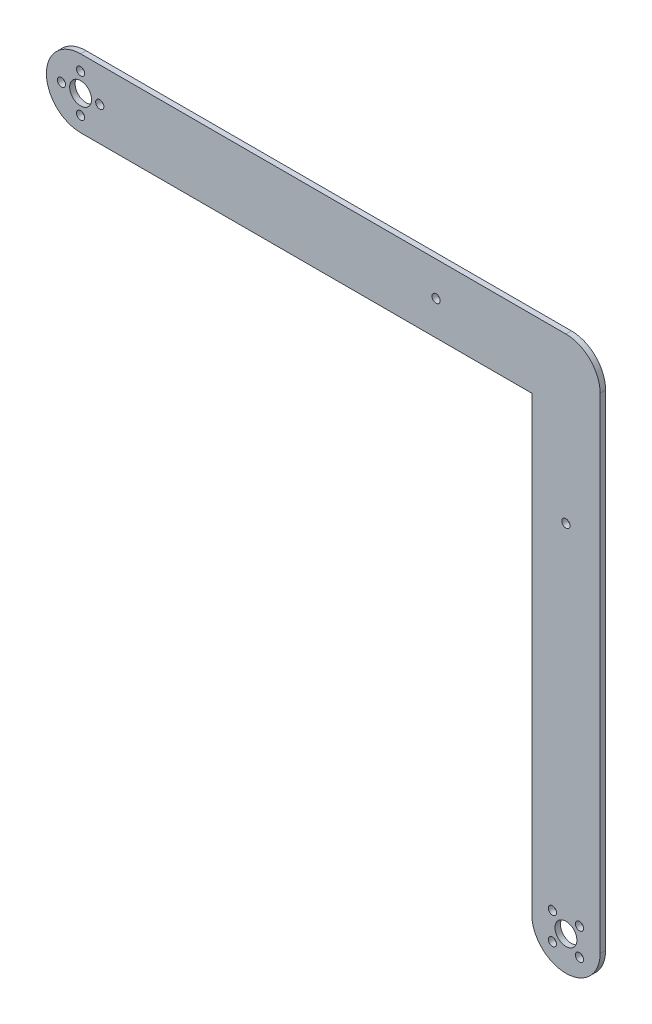
SolidWorks part; units mm, degrees
ref_plane "Front" through (0, 0, 0) normal (0, 0, 1) x (1, 0, 0)
ref_plane "Top" through (0, 0, 0) normal (0, 1, 0) x (1, 0, 0)
ref_plane "Right" through (0, 0, 0) normal (1, 0, 0) x (0, 0, -1)
sketch "草图1" plane through (0, 0, 0) normal (0, 0, 1) x (1, 0, 0)
  line L1 (12.5, 0) -> (12.5, 177.5)
  line L5 (-177.5, 165) -> (-12.5, 165)
  line L6 (0, 190) -> (-177.5, 190)
  line L7 (-12.5, 0) -> (-12.5, 165)
  circle A2 centre (0, 0) radius 4
  circle A22 centre (0, 130) radius 1.5
  circle A26 centre (4.9497, 4.9497) radius 1.5
  circle A27 centre (4.9497, -4.9497) radius 1.5
  circle A28 centre (-4.9497, -4.9497) radius 1.5
  circle A29 centre (-4.9497, 4.9497) radius 1.5
  arc A31 (-12.5, 0) -> (12.5, 0) centre (0, 0) ccw
  arc A32 (-177.5, 190) -> (-177.5, 165) centre (-177.5, 177.5) ccw
  circle A33 centre (-177.5, 177.5) radius 4
  circle A35 centre (-177.5, 184.5) radius 1.5
  circle A36 centre (-170.5, 177.5) radius 1.5
  circle A37 centre (-177.5, 170.5) radius 1.5
  circle A38 centre (-184.5, 177.5) radius 1.5
  circle A39 centre (-47.5, 177.5) radius 1.5
  arc A40 (12.5, 177.5) -> (0, 190) centre (0, 177.5) ccw
  point P16 (0, 0)
  point P34 (-177.5, 177.5)
  point P40 (0, 0)
extrude "凸台-拉伸2" add sketch "草图1" along normal blind 2
